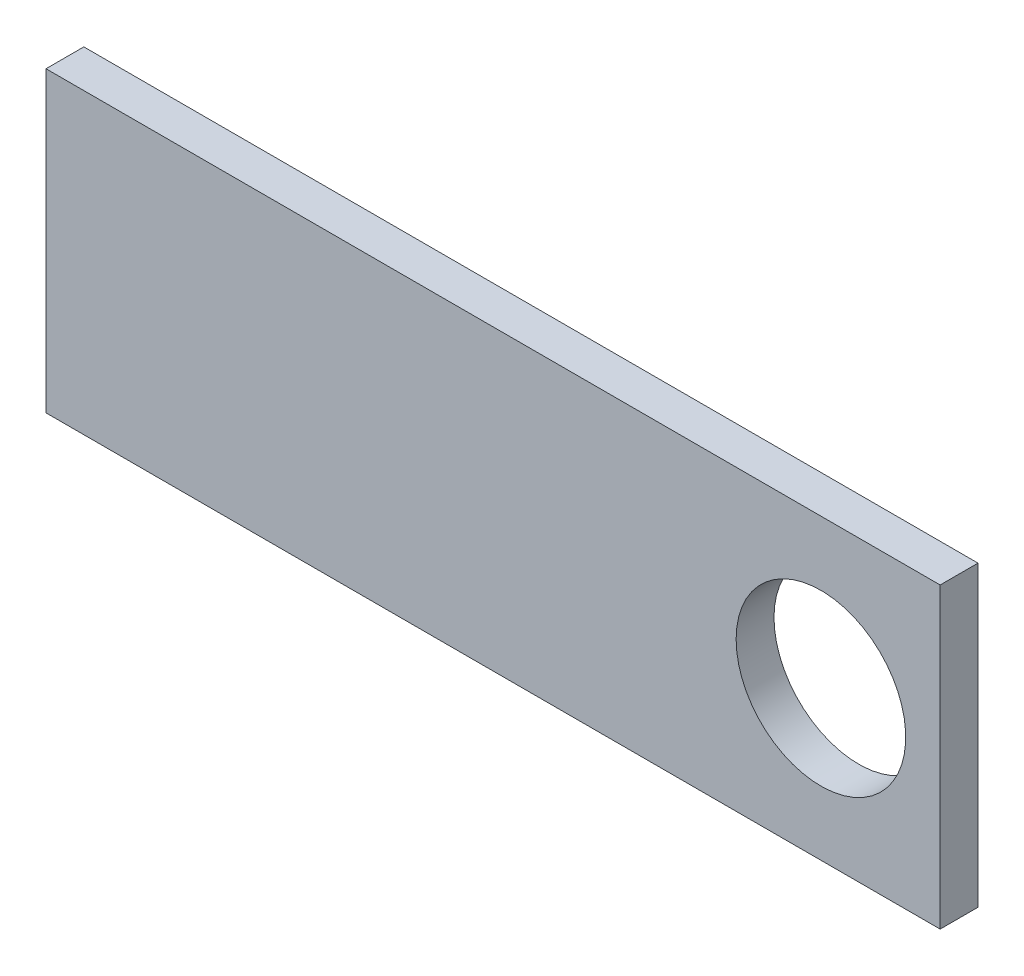
SolidWorks part; units mm, degrees
ref_plane "Front Plane" through (0, 0, 0) normal (0, 0, 1) x (1, 0, 0)
ref_plane "Top Plane" through (0, 0, 0) normal (0, 1, 0) x (1, 0, 0)
ref_plane "Right Plane" through (0, 0, 0) normal (1, 0, 0) x (0, 0, -1)
sketch "Sketch1" plane through (0, 0, 0) normal (0, 0, 1) x (1, 0, 0)
  line L1 (0, 0) -> (150, 0)
  line L2 (0, 0) -> (0, -50)
  line L3 (0, -50) -> (150, -50)
  line L4 (150, 0) -> (150, -50)
  dimension "D1" = 50
  dimension "D2" = 150
extrude "Boss-Extrude1" add sketch "Sketch1" along normal blind 6.35
sketch "Sketch2" plane through (0, 0, 0) normal (0, 0, -1) x (-1, 0, 0)
  line L0 (-150, -50) -> (-150, 0) construction
  line L1 (-150, -25) -> (-110.7339, -25) construction
  circle A0 centre (-130, -25) radius 14.225
  point P2 (0, 0)
  point P6 (-150, -25)
  dimension "D1" = 28.45
  dimension "D2" = 20
extrude "Cut-Extrude1" cut sketch "Sketch2" against normal through all
